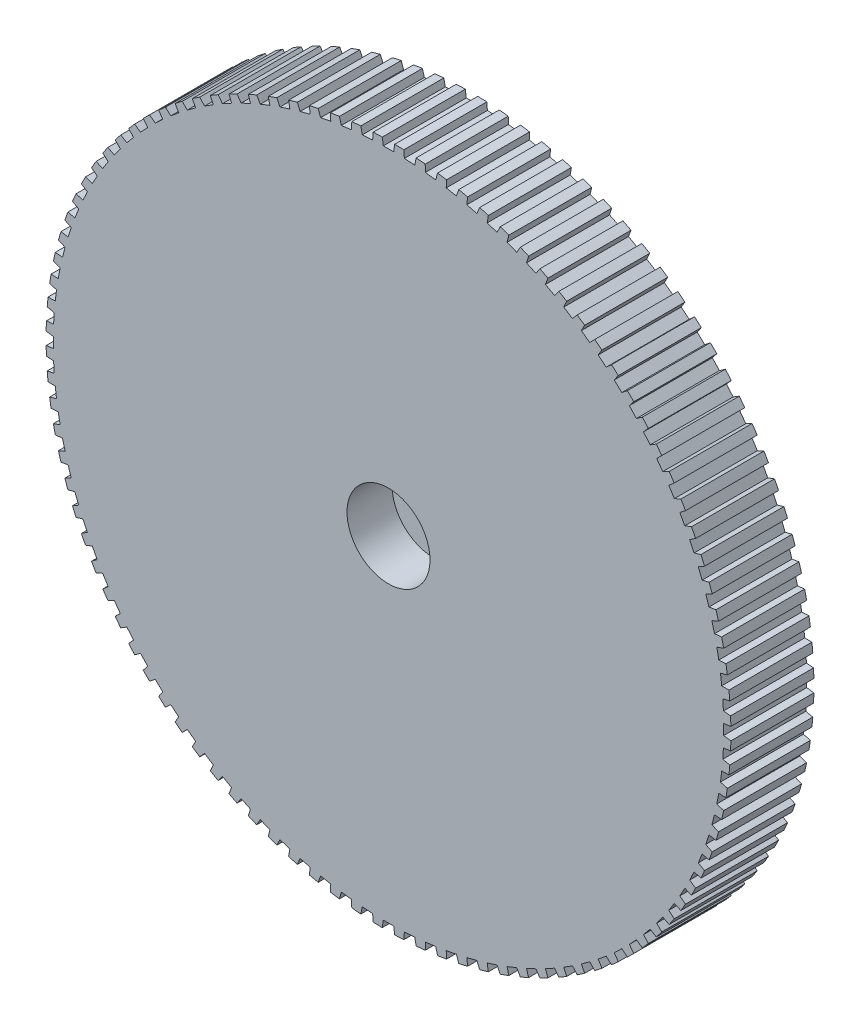
SolidWorks part; units mm, degrees
ref_plane "Front Plane" through (0, 0, 0) normal (0, 0, 1) x (1, 0, 0)
ref_plane "Top Plane" through (0, 0, 0) normal (0, 1, 0) x (1, 0, 0)
ref_plane "Right Plane" through (0, 0, 0) normal (1, 0, 0) x (0, 0, -1)
sketch "Sketch1" plane through (0, 0, 0) normal (0, 0, 1) x (1, 0, 0)
  circle A0 centre (0, 0) radius 37 construction
  circle A2 centre (0, 0) radius 33
  dimension "D1" = 74
  dimension "rubberthk" = 4
extrude "Boss-Extrude1" add sketch "Sketch1" along normal blind 8
sketch "Sketch4" plane through (0, 0, 0) normal (0, 0, -1) x (-1, 0, 0)
  circle A0 centre (0, 0) radius 4.85
  dimension "D1" = 9.7
extrude "Boss-Extrude2" add sketch "Sketch4" along normal blind 8
sketch "Sketch2" plane through (0, 0, 8) normal (0, 0, 1) x (1, 0, 0)
  circle A0 centre (0, 0) radius 4
  dimension "D1" = 8
extrude "Cut-Extrude1" cut sketch "Sketch2" against normal blind 4.35
sketch "Sketch5" plane through (0, 0, 3.65) normal (0, 0, 1) x (1, 0, 0)
  circle A0 centre (0, 0) radius 2
  dimension "D1" = 4
extrude "Cut-Extrude2" cut sketch "Sketch5" against normal offset from surface (4.15 mm away) 7.5 up to face at (-4.85, 0, -8)
sketch "Sketch6" plane through (0, 0, -8) normal (0, 0, -1) x (-1, 0, 0)
  line L0 (2.0347, 1.85) -> (-2.0347, 1.85)
  line L1 (-2.0347, -1.85) -> (2.0347, -1.85)
  arc A0 (2.0347, -1.85) -> (2.0347, 1.85) centre (0, 0) ccw
  arc A1 (-2.0347, 1.85) -> (-2.0347, -1.85) centre (0, 0) ccw
  dimension "D2" = 5.5
  dimension "D1" = 3.7
extrude "Cut-Extrude3" cut sketch "Sketch6" against normal up to surface (7.5 mm away) up to face at (-2, 0, -0.5)
sketch "Sketch7" plane through (0, 0, 8) normal (0, 0, 1) x (1, 0, 0)
  line L0 (-0.6, 32.9945) -> (-0.5, 32.31)
  line L1 (-0.5, 32.31) -> (0.5, 32.31)
  line L2 (0.5, 32.31) -> (0.6, 32.9945)
  line L3 (0, 0) -> (-0.6, 32.9945) construction
  line L4 (0, 0) -> (0.6, 32.9945) construction
  circle A0 centre (0, 0) radius 33 construction
  arc A1 (0.6, 32.9945) -> (-0.6, 32.9945) centre (0, 0) ccw
  point P8 (0, 32.31)
  dimension "D1" = 1
  dimension "D2" = 1.2
  dimension "D3" = 0.69
extrude "Cut-Extrude4" cut sketch "Sketch7" against normal through all
pattern_circular "CirPattern1" count 100 over 360 about axis through (0, 0, 8) along (0, 0, -1) of "Cut-Extrude4"
equation "\"width\"= 24"
equation "\"thk\"= 3"
equation "\"holesize\"= 4.2"
equation "\"holedistance\"= ( 20 + 12 ) / 2"
equation "\"threaded_hole\"= 3.9"
equation "\"fillet_radius\"= 2"
equation "\"ground_clearance\"= 25"
equation "\"tire_thk\"= 4"
equation "\"innerwheel_diam\" = \"wheel_diam\"-2*\"tire_thk\""
equation "\"innerwheel_thk\"= 8"
equation "\"wheel_diam\"= 2*(\"width\"/2+\"ground_clearance\")"
equation "\"D1@Sketch1\"=\"wheel_diam\""
equation "\"rubberthk@Sketch1\"=\"tire_thk\""
equation "\"D1@Boss-Extrude1\"=\"innerwheel_thk\""
